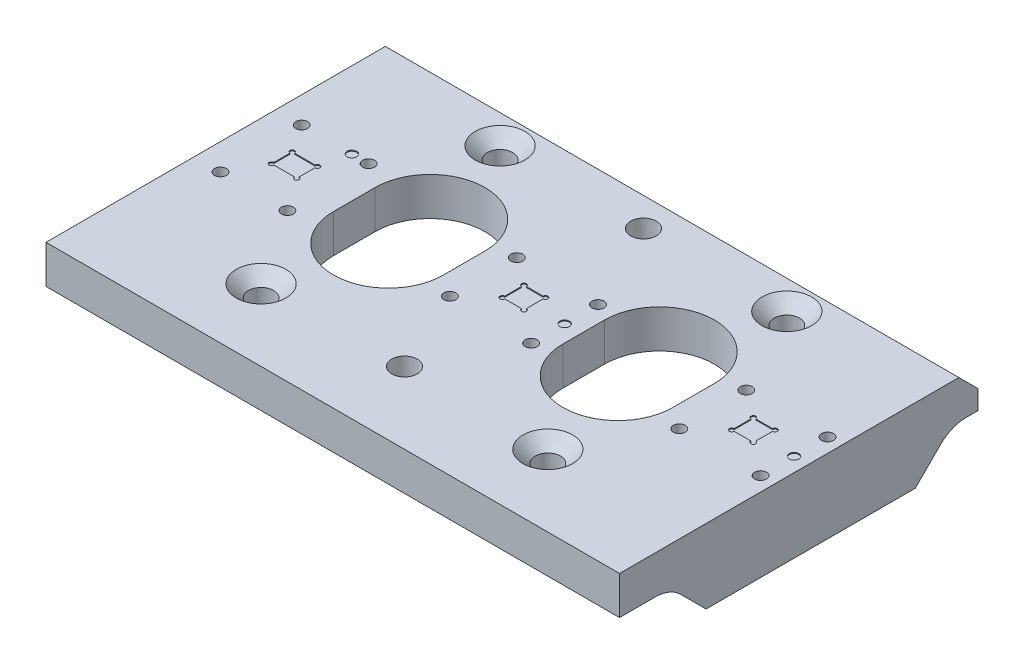
SolidWorks part; units mm, degrees
material "6061 Сплав"
ref_plane "Спереди" through (0, 0, 0) normal (0, 0, 1) x (1, 0, 0)
ref_plane "Сверху" through (0, 0, 0) normal (0, 1, 0) x (1, 0, 0)
ref_plane "Справа" through (0, 0, 0) normal (1, 0, 0) x (0, 0, -1)
sketch "Эскиз5" plane through (0, 0, 0) normal (0, 1, 0) x (1, 0, 0)
  line L1 (0, -40) -> (120, -40)
  line L2 (0, -40) -> (0, 35)
  line L3 (0, 35) -> (120, 35)
  line L4 (120, -40) -> (120, 35)
  line L5 (0, -40) -> (120, 35) construction
  line L6 (0, 35) -> (120, -40) construction
  point P5 (60, -2.5)
extrude "Бобышка-Вытянуть2" add sketch "Эскиз5" against normal blind 8
ref_axis "Ось1" through (120, 0, 2.5) along (-1, 0, 0)
sketch "Sketch2" plane through (0, 0, 0) normal (0, 1, 0) x (1, 0, 0)
  line L0 (40, 35) -> (40, -40) construction
  line L1 (106.24, -2.26) -> (109.76, -2.26)
  line L2 (105.74, -1.76) -> (105.74, 1.76)
  line L3 (106.24, 2.26) -> (109.76, 2.26)
  line L4 (110.26, -1.76) -> (110.26, 1.76)
  line L5 (105.74, -2.26) -> (110.26, 2.26) construction
  line L6 (105.74, 2.26) -> (110.26, -2.26) construction
  line L7 (0, 35) -> (120, 35) construction
  line L8 (0, -40) -> (120, -40) construction
  line L9 (80, 35) -> (80, -40) construction
  line L11 (58.24, -2.26) -> (61.76, -2.26)
  line L18 (57.74, -1.76) -> (57.74, 1.76)
  line L19 (58.24, 2.26) -> (61.76, 2.26)
  line L20 (62.26, -1.76) -> (62.26, 1.76)
  line L21 (57.74, -2.26) -> (62.26, 2.26) construction
  line L22 (57.74, 2.26) -> (62.26, -2.26) construction
  circle A0 centre (117.027, -0.519) radius 1
  circle A1 centre (69.027, -0.519) radius 1
  arc A2 (62.26, 1.76) -> (61.76, 2.26) centre (62.26, 2.26) ccw
  arc A3 (61.76, -2.26) -> (62.26, -1.76) centre (62.26, -2.26) ccw
  arc A4 (58.24, 2.26) -> (57.74, 1.76) centre (57.74, 2.26) ccw
  arc A5 (57.74, -1.76) -> (58.24, -2.26) centre (57.74, -2.26) ccw
  arc A6 (109.76, -2.26) -> (110.26, -1.76) centre (110.26, -2.26) ccw
  arc A7 (110.26, 1.76) -> (109.76, 2.26) centre (110.26, 2.26) ccw
  arc A8 (106.24, 2.26) -> (105.74, 1.76) centre (105.74, 2.26) ccw
  arc A9 (105.74, -1.76) -> (106.24, -2.26) centre (105.74, -2.26) ccw
  point P0 (108, 0)
  point P1 (108, 0)
  point P2 (108, 0)
  point P5 (108, 0)
  point P6 (108, 0)
  point P7 (117.027, -0.519)
  point P8 (117.027, 6.481)
  point P9 (117.027, -7.519)
  point P10 (100.027, -7.519)
  point P11 (100.027, 6.481)
  point P23 (60, 0)
  point P24 (60, 0)
  point P25 (60, 0)
  point P28 (60, 0)
  point P29 (60, 0)
  point P30 (69.027, -0.519)
  point P46 (69.027, 6.481)
  point P47 (69.027, -7.519)
  point P48 (52.027, -7.519)
  point P49 (52.027, 6.481)
  dimension "D21" = 4.52
  dimension "D25" = 0.5
  dimension "D26" = 0.5
  dimension "D1" = 9.027
  dimension "D2" = 7.973
  dimension "D3" = 6.481
  dimension "D4" = 7.519
  dimension "D5" = 7.973
  dimension "D6" = 9.027
  dimension "D7" = 7.519
  dimension "D8" = 6.481
  dimension "D9" = 7
  dimension "D10" = 9.027
  dimension "D11" = 9.027
  dimension "D12" = 7.973
  dimension "D13" = 6.481
  dimension "D14" = 7.519
  dimension "D15" = 7.973
  dimension "D16" = 9.027
  dimension "D17" = 7.519
  dimension "D18" = 6.481
  dimension "D19" = 7
  dimension "D20" = 9.027
  dimension "D22" = 4.52
  dimension "D23" = 4.52
  dimension "D24" = 4.52
extrude "Cut-Extrude2" cut sketch "Sketch2" against normal blind 0.2
sketch "Sketch3" plane through (0, 0, 0) normal (0, 1, 0) x (1, 0, 0)
  line L0 (9.86, -2.16) -> (14.14, -2.16)
  line L1 (9.36, -1.66) -> (9.36, 1.66)
  line L2 (9.86, 2.16) -> (14.14, 2.16)
  line L3 (14.64, -1.66) -> (14.64, 1.66)
  line L4 (9.36, -2.16) -> (14.64, 2.16) construction
  line L5 (9.36, 2.16) -> (14.64, -2.16) construction
  circle A0 centre (16, 8) radius 1
  arc A1 (14.64, 1.66) -> (14.14, 2.16) centre (14.64, 2.16) ccw
  arc A2 (9.86, 2.16) -> (9.36, 1.66) centre (9.36, 2.16) ccw
  arc A3 (9.36, -1.66) -> (9.86, -2.16) centre (9.36, -2.16) ccw
  arc A4 (14.14, -2.16) -> (14.64, -1.66) centre (14.64, -2.16) ccw
  point P1 (12, 0)
  point P2 (12, 0)
  point P9 (5.5, 8)
  point P10 (19.5, 8)
  point P11 (19.5, -9)
  point P12 (5.5, -9)
  dimension "D11" = 5.28
  dimension "D1" = 8
  dimension "D2" = 9
  dimension "D3" = 6.5
  dimension "D4" = 7.5
  dimension "D5" = 6.5
  dimension "D6" = 7.5
  dimension "D7" = 9
  dimension "D8" = 8
  dimension "D9" = 3.5
  dimension "D10" = 8
  dimension "D12" = 4.32
extrude "Cut-Extrude3" cut sketch "Sketch3" against normal blind 0.2
hole_wizard "M3x0.5 Tapped Hole1" positions "Sketch5" profile "Sketch4" tap size "M3x0.5" standard "ANSI Metric"
sketch "Sketch5" plane through (0, 0, 0) normal (0, 1, 0) x (1, 0, 0)
  point P0 (5.5, 8)
  point P3 (19.5, 8)
  point P6 (19.5, -9)
  point P9 (5.5, -9)
  point P12 (52.027, 6.481)
  point P15 (69.027, 6.481)
  point P18 (69.027, -7.519)
  point P21 (52.027, -7.519)
  point P24 (100.027, 6.481)
  point P27 (117.027, 6.481)
  point P30 (117.027, -7.519)
  point P33 (100.027, -7.519)
sketch "Sketch4" plane through (5.5, 0, -8) normal (1, 0, 0) x (0, 0, 1)
  line L0 (0, 0) -> (0, 6.2511)
  line L1 (0, 6.2511) -> (1.25, 5.5)
  line L2 (1.25, 5.5) -> (1.25, 0)
  line L5 (1.25, 0) -> (0, 0)
  line L10 (0, 6.2511) -> (-1.25, 5.5) construction
  line L11 (0, -6.35) -> (0, 107.95) construction
  dimension "Tap Drill Dia." = 2.5
  dimension "Tap Drill Depth" = 5.5
  dimension "Drill Angle" = 118
cosmetic thread "Hole Thread1" [suppressed] parameters "D1"=4, "D2"=3
cosmetic thread "Hole Thread2" [suppressed] parameters "D1"=4, "D2"=3
cosmetic thread "Hole Thread3" [suppressed] parameters "D1"=4, "D2"=3
cosmetic thread "Hole Thread4" [suppressed] parameters "D1"=4, "D2"=3
cosmetic thread "Hole Thread5" [suppressed] parameters "D1"=4, "D2"=3
cosmetic thread "Hole Thread6" [suppressed] parameters "D1"=4, "D2"=3
cosmetic thread "Hole Thread7" [suppressed] parameters "D1"=4, "D2"=3
cosmetic thread "Hole Thread8" [suppressed] parameters "D1"=4, "D2"=3
cosmetic thread "Hole Thread9" [suppressed] parameters "D1"=4, "D2"=3
cosmetic thread "Hole Thread10" [suppressed] parameters "D1"=4, "D2"=3
cosmetic thread "Hole Thread11" [suppressed] parameters "D1"=4, "D2"=3
cosmetic thread "Hole Thread12" [suppressed] parameters "D1"=4, "D2"=3
sketch "Sketch7" plane through (0, 0, 0) normal (0, 1, 0) x (1, 0, 0)
  line L0 (-59.5, 6) -> (150, 6) construction
  line L1 (-59.5, -6) -> (150, -6) construction
  point P4 (36, 6)
  point P5 (60, 6)
  point P6 (84, 6)
  point P7 (84, -6)
  point P8 (60, -6)
  point P9 (36, -6)
sketch "Sketch10" plane through (0, 0, 0) normal (0, 1, 0) x (1, 0, 0)
  line L1 (30, -25) -> (90, -25) construction
  line L2 (30, -25) -> (30, 25) construction
  line L3 (30, 25) -> (90, 25) construction
  line L4 (90, -25) -> (90, 25) construction
  line L5 (30, -25) -> (90, 25) construction
  line L6 (30, 25) -> (90, -25) construction
  point P0 (60, 0)
  point P1 (60, 0)
  point P7 (30, 25)
  point P8 (90, 25)
  point P9 (90, -25)
  point P10 (30, -25)
sketch "Sketch6" plane through (0, -8, 0) normal (0, -1, 0) x (1, 0, 0)
  line L0 (-60, 0) -> (180, 0) construction
  line L1 (60, 29.3879) -> (60, -33.0482) construction
  line L2 (30, -25) -> (90, -25) construction
  line L3 (30, 25) -> (90, 25) construction
  circle A2 centre (60, -25) radius 2.6
  circle A3 centre (60, 25) radius 2.6
  point P4 (60, 25)
  point P5 (60, -25)
  point P6 (60, 25)
  point P9 (60, -25)
hole_wizard "Зенковка для  винта с плоской головкой M51" positions "Sketch12" profile "Sketch11" countersink size "M5" standard "Ansi Metric" end condition through all
sketch "Sketch12" plane through (0, 0, 0) normal (0, 1, 0) x (1, 0, 0)
  point P0 (30, 25)
  point P3 (90, 25)
  point P6 (90, -25)
  point P9 (30, -25)
sketch "Sketch11" plane through (30, 0, -25) normal (1, 0, 0) x (0, 0, 1)
  line L0 (0, 0) -> (0, 8)
  line L1 (0, 8) -> (2.65, 8)
  line L2 (2.65, 8) -> (2.65, 2.55)
  line L3 (2.65, 2.55) -> (5.2, 0)
  line L5 (5.2, 0) -> (0, 0)
  line L6 (-2.65, 2.55) -> (-5.2, 0) construction
  line L11 (0, -6.35) -> (0, 107.95) construction
  dimension "Thru Hole Dia." = 5.3
  dimension "Thru Hole Depth" = 8
  dimension "Near C'Sink Dia." = 10.4
  dimension "Near C'Sink Angle" = 90
extrude "Cut-Extrude4" cut sketch "Sketch6" against normal through all draft 0.573 draft outward yes
sketch "Эскиз7" plane through (0, 0, 0) normal (0, 1, 0) x (1, 0, 0)
  line L7 (120, 35) -> (0, -35) construction
  line L9 (120, -35) -> (0, 35) construction
  line L20 (24.5, 12.0156) -> (24.5, -11.9982) construction
  line L21 (47.5, 12.0156) -> (47.5, -11.9982) construction
  line L22 (72.5, 12.0156) -> (72.5, -11.9982) construction
  line L25 (36, 4.3542) -> (36, -4.3542) construction
  line L26 (47.5, 4.3542) -> (47.5, -4.3542)
  line L27 (24.5, 4.3542) -> (24.5, -4.3542)
  line L28 (95.5, 12.0156) -> (95.5, -11.9982) construction
  line L31 (84, 4.3542) -> (84, -4.3542) construction
  line L32 (95.5, 4.3542) -> (95.5, -4.3542)
  line L33 (72.5, 4.3542) -> (72.5, -4.3542)
  circle A0 centre (30, 25) radius 10 construction
  circle A1 centre (60, 25) radius 10 construction
  circle A2 centre (90, 25) radius 10 construction
  circle A3 centre (30, -25) radius 10 construction
  circle A4 centre (60, -25) radius 10 construction
  circle A5 centre (90, -25) radius 10 construction
  arc A6 (47.5, 4.3542) -> (24.5, 4.3542) centre (36, 4.3542) ccw
  arc A7 (24.5, -4.3542) -> (47.5, -4.3542) centre (36, -4.3542) ccw
  arc A8 (95.5, 4.3542) -> (72.5, 4.3542) centre (84, 4.3542) ccw
  arc A9 (72.5, -4.3542) -> (95.5, -4.3542) centre (84, -4.3542) ccw
  point P0 (60, 25)
  point P1 (60, 0)
  point P6 (60, -25)
  point P12 (5.5, 8)
  point P73 (36, 0)
  point P81 (84, 0)
  dimension "D1" = 12.5
  dimension "D2" = 12.5
  dimension "D3" = 12.5
  dimension "D4" = 12.5
extrude "Вырез-Вытянуть1" cut sketch "Эскиз7" against normal blind 10
sketch "Эскиз8" plane through (120, 0, 0) normal (1, 0, 0) x (0, 0, -1)
  line L0 (-40, -8) -> (35, -8) construction
  line L1 (-32.5, -15.5) -> (32.5, -15.5) construction
  line L2 (-21.8934, -15.5) -> (21.8934, -15.5)
  line L3 (0, 13.3353) -> (0, -32.1616) construction
  line L4 (21.8934, -15.5) -> (27.1967, -10.1967)
  line L5 (-21.8934, -15.5) -> (-27.1967, -10.1967)
  line L6 (-32.5, -8) -> (32.5, -8)
  arc A0 (-27.1967, -10.1967) -> (-32.5, -8) centre (-32.5, -15.5) ccw
  arc A1 (32.5, -8) -> (27.1967, -10.1967) centre (32.5, -15.5) ccw
  point P7 (0, -15.5)
  point P15 (0, -15.5)
  point P17 (-32.5, -8)
  point P19 (32.5, -8)
  dimension "D1" = 15
  dimension "D2" = 45
  dimension "D3" = 7.5
  dimension "D4" = 65
extrude "Бобышка-Вытянуть3" add sketch "Эскиз8" against normal through all
sketch "Эскиз9" plane through (0, 0, 40) normal (0, 0, 1) x (1, 0, 0)
  line L0 (0, -8) -> (120, -8) construction
  line L1 (14, -27.208) -> (106, -27.208)
  line L2 (14, -27.208) -> (14, -8)
  line L3 (14, -8) -> (106, -8)
  line L4 (106, -27.208) -> (106, -8)
  line L11 (0, -8) -> (0, 0) construction
  line L12 (120, -8) -> (120, 0) construction
  dimension "D1" = 14
  dimension "D2" = 14
extrude "Вырез-Вытянуть3" cut sketch "Эскиз9" against normal through all
chamfer "Фаска1" distance 4 angle 45 1 edges at (60, 0, -35)
